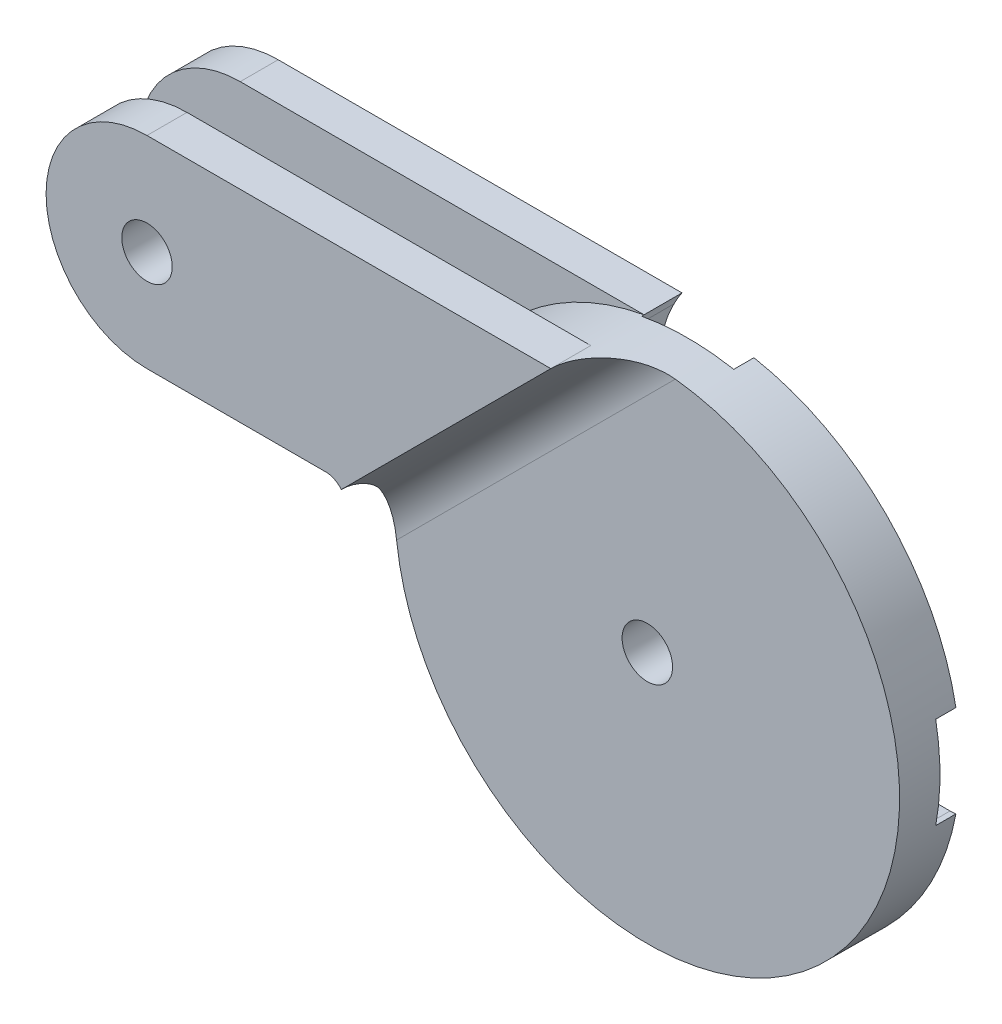
SolidWorks part; units mm, degrees
ref_plane "Front Plane" through (0, 0, 0) normal (0, 0, 1) x (1, 0, 0)
ref_plane "Top Plane" through (0, 0, 0) normal (0, 1, 0) x (1, 0, 0)
ref_plane "Right Plane" through (0, 0, 0) normal (1, 0, 0) x (0, 0, -1)
sketch "Sketch1" plane through (0, 0, 0) normal (0, 0, 1) x (1, 0, 0)
  circle A0 centre (20.1168, -5.969) radius 15.875
  dimension "D1" = 31.75
extrude "Boss-Extrude1" add sketch "Sketch1" along normal blind 2.54 and the other way blind 1.27
sketch "Sketch2" plane through (0, 0, 2.54) normal (0, 0, 1) x (1, 0, 0)
  line L0 (20.1168, 9.906) -> (20.1168, -5.969) construction
  circle A0 centre (20.1168, -5.969) radius 15.875 construction
  circle A1 centre (20.1168, -5.969) radius 1.5875
  dimension "D1" = 3.175
extrude "Cut-Extrude1" cut sketch "Sketch2" against normal through all
sketch "Sketch3" plane through (0, 0, -1.27) normal (0, 0, -1) x (-1, 0, 0)
  line L1 (-23.0378, -3.048) -> (-23.0378, 9.271)
  line L2 (-17.1958, -3.048) -> (-17.1958, 9.271)
  line L3 (-17.1958, -8.89) -> (-4.8768, -8.89)
  line L4 (-17.1958, -3.048) -> (-4.8768, -3.048)
  line L5 (-17.1958, -5.969) -> (-4.8768, -5.969) construction
  line L6 (-23.0378, -8.89) -> (-23.0378, -21.209)
  line L7 (-17.1958, -8.89) -> (-17.1958, -21.209)
  line L9 (-23.0378, -3.048) -> (-35.3568, -3.048)
  line L10 (-23.0378, -8.89) -> (-35.3568, -8.89)
  circle A1 centre (-20.1168, -5.969) radius 15.875
  circle A2 centre (-20.1168, -5.969) radius 15.875
  arc A3 (-17.1958, 9.271) -> (-23.0378, 9.271) centre (-20.1168, 9.271) ccw
  arc A5 (-4.8768, -8.89) -> (-4.8768, -3.048) centre (-4.8768, -5.969) ccw
  arc A7 (-23.0378, -21.209) -> (-17.1958, -21.209) centre (-20.1168, -21.209) ccw
  arc A9 (-35.3568, -3.048) -> (-35.3568, -8.89) centre (-35.3568, -5.969) ccw
  point P0 (-20.1168, 1.651)
  point P11 (-12.4968, -5.969)
  point P12 (-12.4968, -5.969)
  point P18 (-20.1168, -13.589)
  point P24 (-27.7368, -5.969)
  point P30 (-20.1168, -5.969)
  point P38 (-20.1168, -13.589)
  point P45 (-27.7368, -5.969)
  dimension "D2" = 15.24
  dimension "D3" = 5.842
  dimension "D1" = 0
  dimension "D4" = 4
extrude "Cut-Extrude3" cut sketch "Sketch3" against normal blind 1.27 contours L9 A9 L3 L10 L6 A7 L7 A5 L4 L2 A3 L1 A1 region at (20.1168, -5.969, -1.27)
sketch "Sketch4" plane through (0, 0, -1.27) normal (0, 0, -1) x (-1, 0, 0)
  line L0 (-17.2191, 9.6393) -> (8.1915, 9.6393)
  line L2 (-4.5085, -3.0713) -> (8.1915, -3.0713)
  line L3 (-17.1958, -3.048) -> (-4.8768, -3.048) construction
  line L4 (14.5415, 3.2893) -> (14.5415, 3.2787)
  arc A0 (-4.5085, -3.0713) -> (-17.2191, 9.6393) centre (-20.1168, -5.969) ccw construction
  arc A1 (-4.5085, -3.0713) -> (-17.2191, 9.6393) centre (-20.1168, -5.969) ccw
  arc A2 (14.5415, 3.2787) -> (8.1915, -3.0713) centre (8.1915, 3.2787) cw
  arc A3 (14.5415, 3.2893) -> (8.1915, 9.6393) centre (8.1915, 3.2893) ccw
  circle A4 centre (8.1915, 3.2787) radius 1.5875
  point P12 (14.5415, -3.0713)
  dimension "D1" = 19.05
  dimension "D2" = 6.35
  dimension "D3" = 3.175
extrude "Boss-Extrude2" add sketch "Sketch4" along normal blind 1.27 and the other way blind 1.27
fillet "Fillet1" radius 2.54 1 edges at (8.8915, 5.2563, -1.27)
sketch "Sketch6" plane through (0, 0, 2.54) normal (0, 0, 1) x (1, 0, 0)
  line L3 (17.2191, 9.6393) -> (-8.1915, 9.6393)
  line L4 (-14.5415, 3.2893) -> (-14.5415, 3.2787)
  line L5 (-8.1915, -3.0713) -> (4.5085, -3.0713)
  line L6 (17.2191, 9.6393) -> (-8.1915, 9.6393)
  line L7 (-14.5415, 3.2893) -> (-14.5415, 3.2787)
  line L8 (-8.1915, -3.0713) -> (4.5085, -3.0713)
  circle A0 centre (-8.1915, 3.2787) radius 1.5875 construction
  circle A1 centre (-8.1915, 3.2787) radius 1.5875
  arc A3 (17.2191, 9.6393) -> (4.5085, -3.0713) centre (20.1168, -5.969) ccw
  arc A4 (-8.1915, 9.6393) -> (-14.5415, 3.2893) centre (-8.1915, 3.2893) ccw
  arc A5 (-14.5415, 3.2787) -> (-8.1915, -3.0713) centre (-8.1915, 3.2787) ccw
  arc A6 (17.2191, 9.6393) -> (4.5085, -3.0713) centre (20.1168, -5.969) ccw
  arc A7 (-8.1915, 9.6393) -> (-14.5415, 3.2893) centre (-8.1915, 3.2893) ccw
  arc A8 (-14.5415, 3.2787) -> (-8.1915, -3.0713) centre (-8.1915, 3.2787) ccw
  dimension "D1" = 0
extrude "Boss-Extrude3" add sketch "Sketch6" along normal blind 3.175 separate body
sketch "Sketch7" plane through (0, 0, 2.54) normal (0, 0, 1) x (1, 0, 0)
  line L0 (17.2191, 9.6393) -> (4.5085, -3.0713)
  arc A0 (17.2191, 9.6393) -> (4.5085, -3.0713) centre (20.1168, -5.969) ccw construction
  arc A1 (17.2191, 9.6393) -> (4.5085, -3.0713) centre (20.1168, -5.969) ccw
extrude "Boss-Extrude4" add sketch "Sketch7" along normal blind 3.175
sketch "Sketch8" plane through (0, 0, 0) normal (0, 0, 1) x (1, 0, 0)
  line L3 (17.2191, 9.6393) -> (-8.1915, 9.6393)
  line L4 (-14.5415, 3.2893) -> (-14.5415, 3.2787)
  line L5 (-8.1915, -3.0713) -> (4.5085, -3.0713)
  line L6 (17.2191, 9.6393) -> (-8.1915, 9.6393)
  line L7 (-14.5415, 3.2893) -> (-14.5415, 3.2787)
  line L8 (-8.1915, -3.0713) -> (4.5085, -3.0713)
  arc A3 (17.2191, 9.6393) -> (4.5085, -3.0713) centre (20.1168, -5.969) ccw
  arc A4 (-8.1915, 9.6393) -> (-14.5415, 3.2893) centre (-8.1915, 3.2893) ccw
  arc A5 (-14.5415, 3.2787) -> (-8.1915, -3.0713) centre (-8.1915, 3.2787) ccw
  arc A6 (17.2191, 9.6393) -> (4.5085, -3.0713) centre (20.1168, -5.969) ccw
  arc A7 (-8.1915, 9.6393) -> (-14.5415, 3.2893) centre (-8.1915, 3.2893) ccw
  arc A8 (-14.5415, 3.2787) -> (-8.1915, -3.0713) centre (-8.1915, 3.2787) ccw
  dimension "D1" = 0
extrude "Cut-Extrude4" cut sketch "Sketch8" against normal blind 0.1524
sketch "Sketch9" plane through (0, 0, 2.54) normal (0, 0, -1) x (-1, 0, 0)
  line L3 (-4.5085, -3.0713) -> (8.1915, -3.0713)
  line L4 (14.5415, 3.2787) -> (14.5415, 3.2893)
  line L5 (8.1915, 9.6393) -> (-17.2191, 9.6393)
  line L6 (-4.5085, -3.0713) -> (8.1915, -3.0713)
  line L7 (14.5415, 3.2787) -> (14.5415, 3.2893)
  line L8 (8.1915, 9.6393) -> (-17.2191, 9.6393)
  arc A5 (-4.5085, -3.0713) -> (-17.2191, 9.6393) centre (-20.1168, -5.969) ccw
  arc A7 (8.1915, -3.0713) -> (14.5415, 3.2787) centre (8.1915, 3.2787) ccw
  arc A8 (14.5415, 3.2893) -> (8.1915, 9.6393) centre (8.1915, 3.2893) ccw
  arc A10 (-4.5085, -3.0713) -> (-17.2191, 9.6393) centre (-20.1168, -5.969) ccw
  arc A12 (8.1915, -3.0713) -> (14.5415, 3.2787) centre (8.1915, 3.2787) ccw
  arc A13 (14.5415, 3.2893) -> (8.1915, 9.6393) centre (8.1915, 3.2893) ccw
  dimension "D1" = 0
extrude "Cut-Extrude5" cut sketch "Sketch9" against normal blind 0.6604
fillet "Fillet5" radius 3.175 1 edges at (10.8638, 3.284, 2.54)
fillet "Fillet6" radius 1.27 1 edges at (4.5085, -3.0713, 4.4577)
